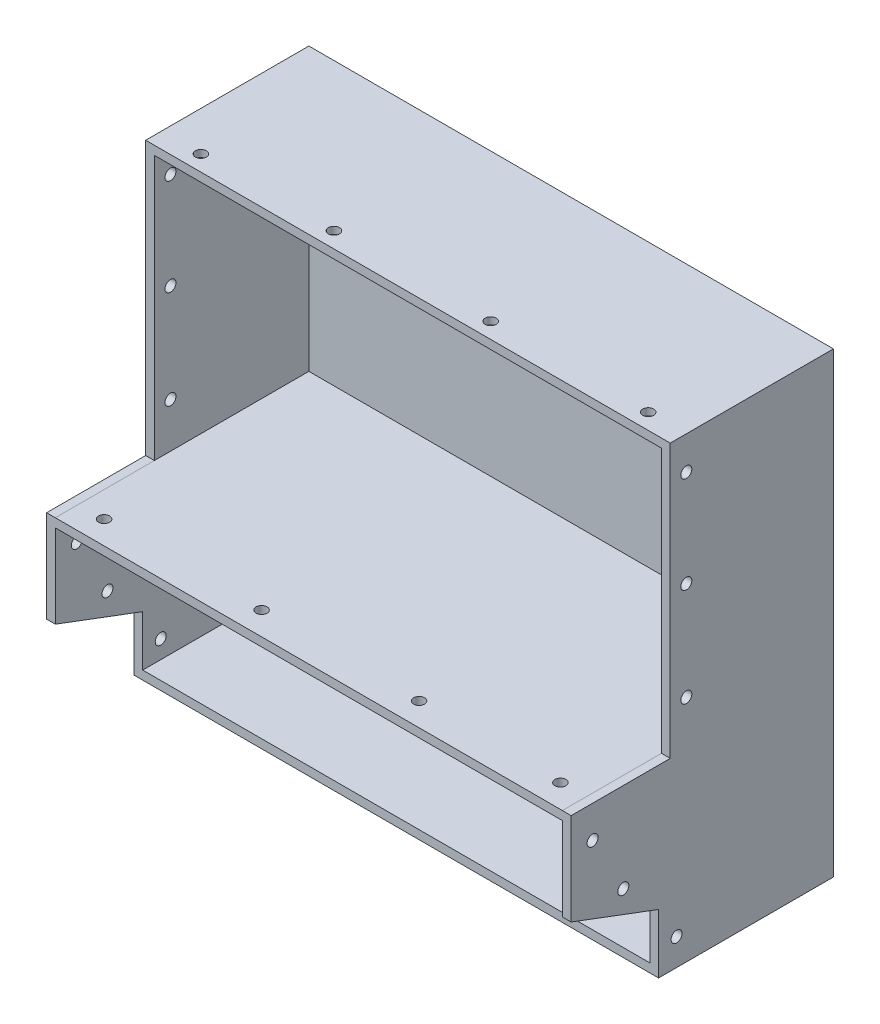
SolidWorks part; units mm, degrees
material "Custom Plastic"
ref_plane "X-Y Datum" through (0, 0, 0) normal (0, 0, 1) x (1, 0, 0)
ref_plane "X-Z Datum" through (0, 0, 0) normal (0, 1, 0) x (1, 0, 0)
ref_plane "Y-Z Datum" through (0, 0, 0) normal (1, 0, 0) x (0, 0, -1)
sketch "Sketch1" plane through (0, 0, 0) normal (0, 0, 1) x (1, 0, 0)
  line L1 (-95.25, -83.058) -> (95.25, -83.058)
  line L2 (-95.25, -83.058) -> (-95.25, 83.058)
  line L3 (-95.25, 83.058) -> (95.25, 83.058)
  line L4 (95.25, -83.058) -> (95.25, 83.058)
  line L5 (-95.25, -83.058) -> (95.25, 83.058) construction
  line L6 (-95.25, 83.058) -> (95.25, -83.058) construction
  point P0 (0, 0)
  dimension "D1" = 166.116
  dimension "D2" = 190.5
extrude "Boss-Extrude1" add sketch "Sketch1" along normal blind 95.25
sketch "Sketch3" plane through (0, 0, 95.25) normal (0, 0, 1) x (1, 0, 0)
  line L0 (-92.075, -49.9618) -> (92.075, -49.9618)
  line L1 (92.075, -61.8913) -> (95.25, -61.8913)
  line L2 (-92.075, -61.8913) -> (92.075, -61.8913)
  line L3 (95.25, -83.058) -> (95.25, 83.058) construction
  line L4 (-92.075, -61.8913) -> (-92.075, -79.883)
  line L5 (-95.25, -49.9618) -> (-95.25, -61.8913)
  line L6 (92.075, -61.8913) -> (92.075, -79.883)
  line L7 (-95.25, 83.058) -> (-95.25, -83.058) construction
  line L8 (-122.0928, 3.2687) -> (-122.1486, 3.2687)
  line L9 (92.075, -79.883) -> (76.2531, -79.883)
  line L13 (-95.25, 32.8917) -> (-92.075, 32.8917)
  line L15 (-122.0786, -16.0951) -> (-122.1486, -16.0951)
  line L17 (95.25, -49.9618) -> (92.075, -49.9618)
  line L18 (-92.075, -79.883) -> (76.2531, -79.883)
  line L21 (-92.075, -49.9618) -> (-95.25, -49.9618)
  line L23 (-81.0858, 79.883) -> (83.8833, 79.883)
  line L25 (-81.0858, 79.883) -> (-92.075, 79.883)
  line L26 (-92.075, 79.883) -> (-92.075, -16.0951)
  line L28 (95.25, 48.6627) -> (92.075, 48.6627)
  line L30 (83.8833, 79.883) -> (92.075, 79.883)
  line L31 (92.075, 79.883) -> (92.075, -16.0951)
  line L33 (-92.075, -16.0951) -> (92.075, -16.0951)
  line L34 (95.25, -49.9618) -> (95.25, -61.8913)
  line L35 (-95.25, -61.8913) -> (-92.075, -61.8913)
extrude "Cut-Extrude1" cut sketch "Sketch3" against normal blind 92.075 contours L23 region at (0, 31.8939, 95.25)
sketch "Sketch15" plane through (0, 0, 95.25) normal (0, 0, 1) x (1, 0, 0)
  line L1 (-95.25, 83.058) -> (-95.25, -83.058) construction
  line L3 (95.25, -83.058) -> (95.25, 83.058) construction
  line L4 (95.25, -16.1093) -> (95.25, 83.058)
  line L5 (95.25, 83.058) -> (-95.25, 83.058)
  line L6 (-95.25, 83.058) -> (-95.25, -16.1093)
  line L10 (95.25, -16.1093) -> (92.075, -16.0951)
  line L11 (92.075, -16.0951) -> (92.075, 79.883)
  line L12 (92.075, 79.883) -> (-92.075, 79.883)
  line L13 (-92.075, 79.883) -> (-92.075, -16.0951)
  line L14 (-92.075, -16.0951) -> (92.075, -16.0951) construction
  line L15 (-92.075, 79.883) -> (-92.075, -16.0951) construction
  line L16 (-95.25, -16.1093) -> (-92.075, -16.0951)
extrude "Cut-Extrude5" cut sketch "Sketch15" against normal blind 35.9842
sketch "Sketch17" plane through (0, 0, 95.25) normal (0, 0, 1) x (1, 0, 0)
  line L0 (-95.25, -49.5836) -> (-95.25, -83.058)
  line L2 (-95.25, -83.058) -> (95.25, -83.058)
  line L3 (-95.25, -16.1093) -> (-95.25, -83.058) construction
  line L4 (95.25, -83.058) -> (95.25, -16.1093) construction
  line L5 (95.25, -83.058) -> (95.25, -49.5836)
  line L6 (-95.25, -49.5836) -> (95.25, -49.5836)
extrude "Cut-Extrude6" cut sketch "Sketch17" against normal blind 31.75
sketch "Sketch18" plane through (-95.25, 0, 0) normal (-1, 0, 0) x (0, 0, 1)
  line L0 (63.5, -49.5836) -> (63.5, -61.5061)
  line L1 (63.5, -49.5836) -> (63.5, -83.058) construction
  line L2 (63.5, -61.5061) -> (95.25, -49.5836)
  line L3 (95.25, -49.5836) -> (63.5, -49.5836)
extrude "Boss-Extrude8" add sketch "Sketch18" against normal blind 190.5
sketch "Sketch19" plane through (0, 0, 95.25) normal (0, 0, 1) x (1, 0, 0)
  line L0 (-92.075, -19.2701) -> (-92.075, -49.5836)
  line L2 (95.25, -49.5836) -> (-95.25, -49.5836) construction
  line L4 (92.075, -19.2701) -> (92.075, -49.5836)
  line L6 (92.075, -49.5836) -> (-92.075, -49.5836)
  line L8 (-92.075, -19.2701) -> (92.075, -19.2701)
extrude "Cut-Extrude7" cut sketch "Sketch19" against normal blind 92.075
sketch "Sketch20" plane through (0, -74.8032, 28.0894) normal (0, -0.9362, 0.3515) x (1, 0, 0)
  line L2 (-92.075, -3.8019) -> (-92.075, 82.3961) construction
  line L4 (-92.075, 71.7396) -> (92.075, 71.7396) construction
  line L6 (-92.075, 71.7396) -> (92.075, 71.7396)
  line L12 (92.075, -3.8019) -> (92.075, 82.3961) construction
  line L13 (95.25, 71.7396) -> (92.075, 71.7396) construction
  line L15 (-92.075, 71.7396) -> (-92.075, 37.8249)
  line L16 (95.25, 37.8249) -> (-95.25, 37.8249) construction
  line L17 (92.075, 71.7396) -> (92.075, 37.8249)
  line L18 (92.075, 37.8249) -> (-92.075, 37.8249)
extrude "Cut-Extrude8" cut sketch "Sketch20" against normal blind 13.175
sketch "Sketch21" plane through (0, 0, 63.5) normal (0, 0, 1) x (1, 0, 0)
  line L0 (-92.075, -61.5061) -> (-92.075, -49.5836)
  line L2 (-92.075, -49.5836) -> (92.075, -49.5836)
  line L4 (92.075, -49.5836) -> (92.075, -61.5061)
  line L6 (-92.075, -61.5061) -> (-92.075, -79.883)
  line L7 (-92.075, -79.883) -> (92.075, -79.883)
  line L8 (92.075, -79.883) -> (92.075, -61.5061)
extrude "Cut-Extrude9" cut sketch "Sketch21" against normal blind 60.325
sketch "Sketch23" plane through (0, -83.058, 0) normal (0, -1, 0) x (1, 0, 0)
  circle A4 centre (-82.8492, 55.0007) radius 2
  circle A5 centre (-25.472, 55.0007) radius 2
  circle A6 centre (31.5236, 55.0007) radius 2
  circle A7 centre (82.8147, 55.0007) radius 2
  point P8 (-82.8492, 55.0007)
  point P9 (-25.472, 55.0007)
  point P10 (31.5236, 55.0007)
  point P11 (82.8147, 55.0007)
extrude "Cut-Extrude10" cut sketch "Sketch23" against normal blind 2.54
sketch "Sketch24" plane through (0, 83.058, 0) normal (0, 1, 0) x (1, 0, 0)
  line L0 (81.5233, -53.5508) -> (-86.3243, -53.5508) construction
  line L1 (95.25, -59.2658) -> (-95.25, -59.2658) construction
  circle A0 centre (81.5233, -53.5508) radius 2
  circle A3 centre (24.3357, -53.5508) radius 2
  circle A4 centre (-32.5907, -53.5508) radius 2
  circle A7 centre (-80.8952, -53.5508) radius 2
  point P11 (-32.5907, -53.5508)
  point P12 (-80.8952, -53.5508)
  point P13 (24.3357, -53.5508)
  point P14 (81.5233, -53.5508)
  dimension "D1" = 5.715
extrude "Cut-Extrude11" cut sketch "Sketch24" against normal blind 2.54
sketch "Sketch25" plane through (95.25, 0, 0) normal (1, 0, 0) x (0, 0, -1)
  circle A0 centre (-53.4238, 70.993) radius 2
  circle A1 centre (-53.4238, 35.941) radius 2
  circle A4 centre (-53.4238, 0.889) radius 2 [skipped]
  circle A6 centre (-53.4238, 0.2178) radius 2
  dimension "D2" = 3
extrude "Cut-Extrude12" cut sketch "Sketch25" against normal through all
sketch "Sketch26" plane through (0, -16.0951, 0) normal (0, 1, 0) x (1, 0, 0)
  line L1 (92.075, -59.2658) -> (92.075, -95.25) construction
  line L2 (92.075, -63.7108) -> (-92.075, -63.7108)
  line L3 (-92.075, -59.2658) -> (-92.075, -95.25) construction
  line L5 (-92.075, -79.375) -> (92.075, -79.375)
sketch "Sketch27" plane through (0, -16.0951, 0) normal (0, 1, 0) x (1, 0, 0)
  circle A0 centre (82.9278, -86.8228) radius 2
  circle A8 centre (31.5919, -86.8228) radius 2
  circle A11 centre (-25.6023, -86.8228) radius 2
  circle A12 centre (-82.8005, -86.8228) radius 2
  point P0 (82.9278, -86.8228)
extrude "Cut-Extrude13" cut sketch "Sketch27" against normal blind 3.175
sketch "Sketch28" plane through (95.25, 0, 0) normal (1, 0, 0) x (0, 0, -1)
  circle A0 centre (-56.9612, -73.2851) radius 2
  circle A1 centre (-76.307, -48.5678) radius 2
  circle A2 centre (-87.4498, -27.7945) radius 2
  point P0 (-56.9612, -73.2851)
extrude "Cut-Extrude15" cut sketch "Sketch28" against normal through all
